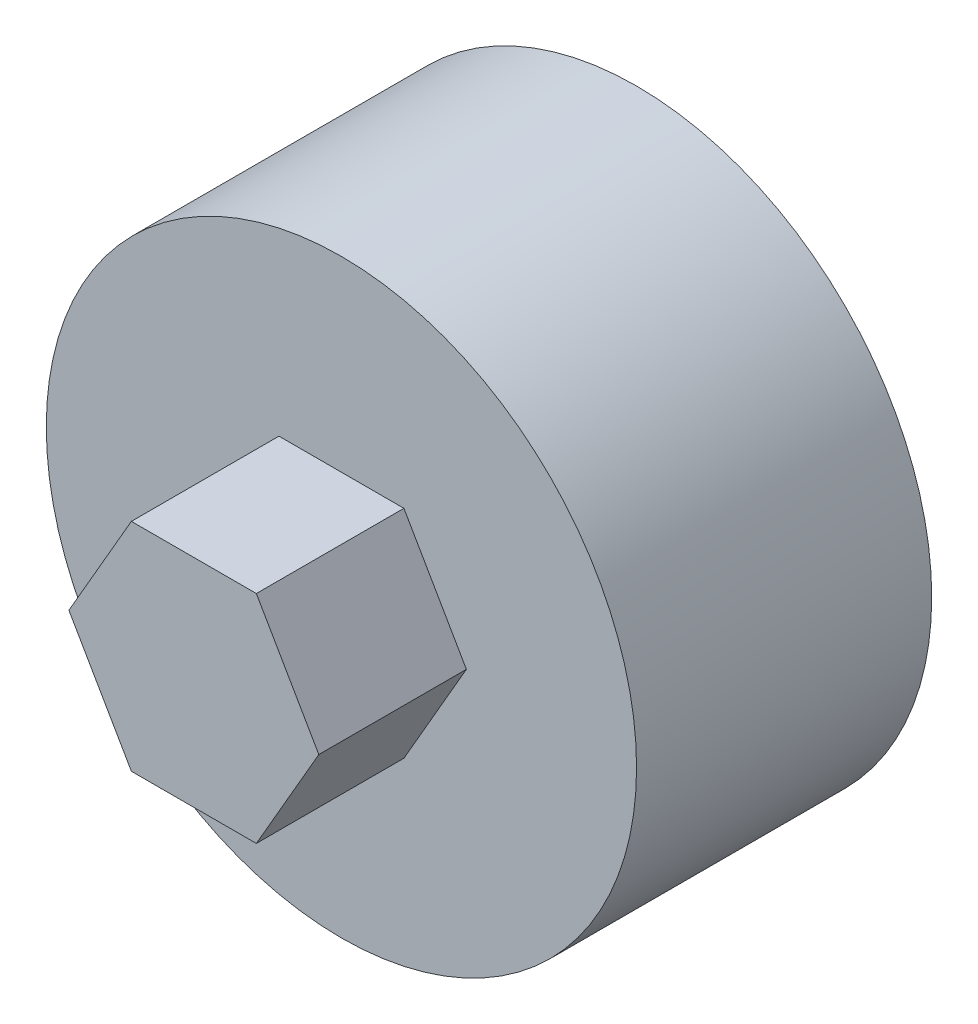
SolidWorks part; units mm, degrees
ref_plane "前视基准面" through (0, 0, 0) normal (0, 0, 1) x (1, 0, 0)
ref_plane "上视基准面" through (0, 0, 0) normal (0, 1, 0) x (1, 0, 0)
ref_plane "右视基准面" through (0, 0, 0) normal (1, 0, 0) x (0, 0, -1)
other "Configuration Table"
sketch "草图1" plane through (0, 0, 0) normal (0, 0, 1) x (1, 0, 0)
  line L0 (0, 0) -> (1.7387, 0.4659) construction
  line L1 (0, 0) -> (1.6291, 0.4551)
  line L2 (0, 0) -> (1.6291, -0.4551)
  line L3 (0, 0) -> (1.7387, -0.4659) construction
  line L4 (0, 0) -> (2.425, 0) construction
  line L5 (1.7387, 0.4659) -> (1.7387, -0.4659) construction
  circle A0 centre (0, 0) radius 1.525
  circle A1 centre (0, 0) radius 2.425
  circle A2 centre (0, 0) radius 1.6914 construction
  circle A3 centre (0, 0) radius 1.8 construction
  circle A4 centre (0, 0) radius 3
  spline S0 degree 4 poles (1.6291, 0.4551) (1.6415, 0.4586) (1.6769, 0.4656) (1.746, 0.4684) (1.8576, 0.4574) (1.9985, 0.4209) (2.171, 0.3489) (2.3582, 0.2351) (2.5438, 0.0819) (2.7191, -0.1093) (2.8693, -0.3205) (2.9946, -0.5472) (3.1006, -0.7975) (3.1986, -1.1195) (3.2658, -1.5159) (3.2754, -1.9832) (3.2064, -2.4974) (3.0631, -2.9965) (2.8558, -3.471) (2.5865, -3.9159) (2.2706, -4.3232) (1.901, -4.6937) (1.507, -5.0164) (1.0559, -5.3028) (0.6986, -5.4883) (0.2793, -5.6591) (0.0342, -5.7399) (-0.2484, -5.8241) (-0.3932, -5.8525) (-0.5197, -5.8826) (-0.5587, -5.8884) (-0.5863, -5.894) (-0.6011, -5.8971) knots 0 0 0 0 0 0.005604 0.015718 0.02996 0.048734 0.068727 0.096889 0.125051 0.153212 0.181374 0.209535 0.237696 0.271429 0.327752 0.384075 0.440398 0.496721 0.553044 0.609367 0.66569 0.722013 0.778336 0.834659 0.890982 0.909091 0.954545 0.977273 0.988636 0.994318 1 1 1 1 1 construction
  spline S1 degree 4 poles (1.6291, 0.4551) (1.6415, 0.4586) (1.6769, 0.4656) (1.746, 0.4684) (1.8576, 0.4574) (1.9985, 0.4209) (2.171, 0.3489) (2.3582, 0.2351) (2.5438, 0.0819) (2.7191, -0.1093) (2.8693, -0.3205) (2.9946, -0.5472) (3.1006, -0.7975) (3.1986, -1.1195) (3.2658, -1.5159) (3.2754, -1.9832) (3.2064, -2.4974) (3.0631, -2.9965) (2.8558, -3.471) (2.5865, -3.9159) (2.2706, -4.3232) (1.901, -4.6937) (1.507, -5.0164) (1.0559, -5.3028) (0.6986, -5.4883) (0.3874, -5.615) (0.2408, -5.6686) (0.2052, -5.6811) knots 0 0 0 0 0 0.005604 0.015718 0.02996 0.048734 0.068727 0.096889 0.125051 0.153212 0.181374 0.209535 0.237696 0.271429 0.327752 0.384075 0.440398 0.496721 0.553044 0.609367 0.66569 0.722013 0.778336 0.834659 0.890982 0.909091 0.909091 0.909091 0.909091 0.909091
  spline S2 degree 4 poles (1.6291, -0.4551) (1.6415, -0.4586) (1.6769, -0.4656) (1.746, -0.4684) (1.8576, -0.4574) (1.9985, -0.4209) (2.171, -0.3489) (2.3582, -0.2351) (2.5438, -0.0819) (2.7191, 0.1093) (2.8693, 0.3205) (2.9946, 0.5472) (3.1006, 0.7975) (3.1986, 1.1195) (3.2658, 1.5159) (3.2754, 1.9832) (3.2064, 2.4974) (3.0631, 2.9965) (2.8558, 3.471) (2.5865, 3.9159) (2.2706, 4.3232) (1.901, 4.6937) (1.507, 5.0164) (1.0559, 5.3028) (0.6986, 5.4883) (0.2793, 5.6591) (0.0342, 5.7399) (-0.2484, 5.8241) (-0.3932, 5.8525) (-0.5197, 5.8826) (-0.5587, 5.8884) (-0.5863, 5.894) (-0.6011, 5.8971) knots 0 0 0 0 0 0.005604 0.015718 0.02996 0.048734 0.068727 0.096889 0.125051 0.153212 0.181374 0.209535 0.237696 0.271429 0.327752 0.384075 0.440398 0.496721 0.553044 0.609367 0.66569 0.722013 0.778336 0.834659 0.890982 0.909091 0.954545 0.977273 0.988636 0.994318 1 1 1 1 1 construction
  spline S3 degree 4 poles (1.6291, -0.4551) (1.6415, -0.4586) (1.6769, -0.4656) (1.746, -0.4684) (1.8576, -0.4574) (1.9985, -0.4209) (2.171, -0.3489) (2.3582, -0.2351) (2.5438, -0.0819) (2.7191, 0.1093) (2.8693, 0.3205) (2.9946, 0.5472) (3.1006, 0.7975) (3.1986, 1.1195) (3.2658, 1.5159) (3.2754, 1.9832) (3.2064, 2.4974) (3.0631, 2.9965) (2.8558, 3.471) (2.5865, 3.9159) (2.2706, 4.3232) (1.901, 4.6937) (1.507, 5.0164) (1.0559, 5.3028) (0.6986, 5.4883) (0.3874, 5.615) (0.2408, 5.6686) (0.2052, 5.6811) knots 0 0 0 0 0 0.005604 0.015718 0.02996 0.048734 0.068727 0.096889 0.125051 0.153212 0.181374 0.209535 0.237696 0.271429 0.327752 0.384075 0.440398 0.496721 0.553044 0.609367 0.66569 0.722013 0.778336 0.834659 0.890982 0.909091 0.909091 0.909091 0.909091 0.909091
  point P16 (1.7387, 0)
  dimension "内啮合齿顶圆直径" = 3.05
  dimension "内啮合分度圆直径" = 3.6
  dimension "内啮合基圆直径" = 3.3829
  dimension "内啮合齿根圆直径" = 4.85
  dimension "外径" = 6
  dimension "渐开线镜像线夹角" = 15
extrude "凸台-拉伸1" add sketch "草图1" along normal blind 2 contours A4 | A0
extrude "切除-拉伸2" cut sketch "草图1<3>" along normal through all contours A0 S3 A1 S1 region at (1.9135, 0, 0)
sketch "草图1<3>" plane through (0, 0, 0) normal (0, 0, 1) x (1, 0, 0) same geometry as "草图1"
pattern_circular "阵列(圆周)1" count 9 over 360 about axis through (0, 0, 2) along (0, 0, 1) of "切除-拉伸2"
sketch "草图2" plane through (0, 0, 2) normal (0, 0, 1) x (1, 0, 0)
  line L1 (0.6351, 1.1) -> (-0.6351, 1.1)
  line L2 (-0.6351, 1.1) -> (-1.2702, 0)
  line L3 (-1.2702, 0) -> (-0.6351, -1.1)
  line L4 (-0.6351, -1.1) -> (0.6351, -1.1)
  line L5 (0.6351, -1.1) -> (1.2702, 0)
  line L6 (1.2702, 0) -> (0.6351, 1.1)
  circle A0 centre (0, 0) radius 3
  circle A1 centre (0, 0) radius 3 construction
  circle A2 centre (0, 0) radius 1.2702
  circle A3 centre (0, 0) radius 1.1 construction
  dimension "D1" = 2.2
extrude "凸台-拉伸2" add sketch "草图2" along normal blind 1 contours A0
extrude "凸台-拉伸3" add sketch "草图2<3>" along normal blind 1.5 from surface contours L1 L2 L3 L4 L5 L6 starting at face at (3, 0, 3)
sketch "草图2<3>" plane through (0, 0, 2) normal (0, 0, 1) x (1, 0, 0) same geometry as "草图2"
equation "\"m\"= 0.4'模数"
equation "\"z1\"= 6'外啮合齿轮数"
equation "\"a\"= 20度'压力角"
equation "\"z2\"= 9'内啮合齿轮数"
equation "\"hax\"= 1'齿顶高系数"
equation "\"cx\"= 0.25'顶隙系数"
equation "\"ha\"= \"hax\" * \"m\"'齿顶高"
equation "\"hf\"= ( \"hax\" + \"cx\" ) * \"m\"'齿根高"
equation "\"d1\"= \"m\" * \"z1\"'外啮合分度圆直径"
equation "\"da1\"= ( \"z1\" + 2 ) * \"m\"'外啮合齿顶圆直径"
equation "\"df1\"= \"d1\" - 2 * \"hf\"'外啮合齿根圆直径"
equation "\"db1\"= \"d1\" * cos ( \"a\" )'外啮合基圆直径"
equation "\"p\"= \"m\" * PI'齿距"
equation "\"d2\"= \"m\" * \"z2\"'内啮合分度圆直径"
equation "\"db2\"= \"d2\" * cos ( \"a\" )'内啮合基圆直径"
equation "\"da2\"= ( \"z2\" - 2 ) * \"m\"'内啮合齿顶圆直径"
equation "\"df2\"= \"d2\" + 2 * \"hf\"'内啮合齿根圆直径"
equation "\"内啮合齿顶圆直径@草图1\" = \"da2\" + 0.5 * \"hf\""
equation "\"内啮合齿根圆直径@草图1\"= \"df2\" + 0.5 * \"hf\""
equation "\"内啮合分度圆直径@草图1\"= \"d2\""
equation "\"内啮合基圆直径@草图1\"= \"db2\""
equation "\"渐开线镜像线夹角@草图1\"= 360度 / 4 / \"z2\" + 360度 / 4 / \"z2\" / 2"
equation "\"do\"= IIF ( \"edo\" >= ( \"df2\" + 1 ) , \"edo\" , ( \"df2\" + 1 ) )'外圈直径"
equation "\"h\"= 2'厚度"
equation "\"外径@草图1\"= \"do\""
equation "\"厚度@凸台-拉伸1\"= \"h\""
equation "\"内啮合齿轮数@阵列(圆周)1\"= \"z2\""
equation "\"edo\"= 6'期望的外圈直径"
